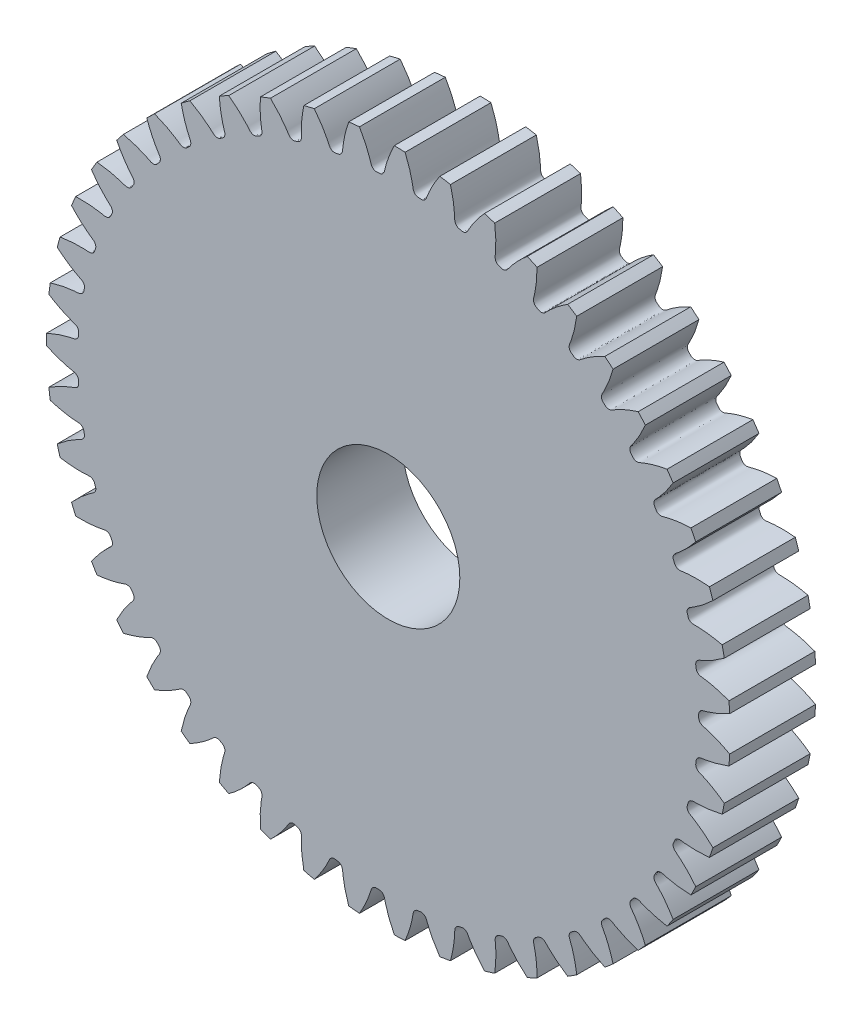
SolidWorks part; units mm, degrees
ref_plane "Front Plane" through (0, 0, 0) normal (0, 0, 1) x (1, 0, 0)
ref_plane "Top Plane" through (0, 0, 0) normal (0, 1, 0) x (1, 0, 0)
ref_plane "Right Plane" through (0, 0, 0) normal (1, 0, 0) x (0, 0, -1)
ref_axis "Axis1" through (0, 0, 55) along (0, 0, -1)
sketch "SketchRevolveSpurGear" plane through (0, 0, 0) normal (1, 0, 0) x (0, 0, -1)
  line L0 (0, 0) -> (1, 0) construction
  line L1 (-0.6, 0) -> (-0.6, 4.7775)
  line L2 (-0.6, 4.7775) -> (0.6, 4.7775)
  line L3 (0.6, 4.7775) -> (0.6, 0)
  line L4 (0.6, 0) -> (-0.6, 0)
  dimension "Side1" = 0.6
  dimension "OutsideRadius" = 4.7775
  dimension "Side2" = 0.6
revolve "SpurGear" add sketch "SketchRevolveSpurGear" angle 360 about L0
sketch "SketchToothSpurGear" plane through (0, 0, 0) normal (0, 0, 1) x (1, 0, 0)
  arc A0 (4.7808, 0.2492) -> (4.7808, -0.2492) centre (0, 0) cw
  spline S0 degree 3 poles (4.7808, -0.2492) (4.7634, -0.2397) (4.7377, -0.2259) (4.7034, -0.2086) (4.6788, -0.1966) (4.6549, -0.1854) (4.6316, -0.1749) (4.6091, -0.1651) (4.5872, -0.156) (4.5661, -0.1476) (4.5457, -0.1398) (4.526, -0.1326) (4.5071, -0.126) (4.489, -0.1199) (4.4717, -0.1144) (4.4552, -0.1095) (4.4272, -0.1013) (4.4005, -0.0961) (4.3781, -0.085) (4.3686, -0.079) (4.3587, -0.0706) (4.3487, -0.0584) (4.341, -0.0417) (4.3379, -0.0214) (4.3392, 0) (4.3379, 0.0214) (4.341, 0.0417) (4.3487, 0.0584) (4.3587, 0.0706) (4.3686, 0.079) (4.3781, 0.085) (4.4005, 0.0961) (4.4272, 0.1013) (4.4552, 0.1095) (4.4717, 0.1144) (4.489, 0.1199) (4.5071, 0.126) (4.526, 0.1326) (4.5457, 0.1398) (4.5661, 0.1476) (4.5872, 0.156) (4.6091, 0.1651) (4.6316, 0.1749) (4.6549, 0.1854) (4.6788, 0.1966) (4.7034, 0.2086) (4.7377, 0.2259) (4.7634, 0.2397) (4.7808, 0.2492) knots 0 0 0 0 0.055398 0.081807 0.107356 0.132045 0.155874 0.178843 0.200952 0.222201 0.242591 0.26212 0.280789 0.298599 0.315548 0.331638 0.346867 0.397347 0.406728 0.416895 0.428636 0.443004 0.46085 0.479253 0.5 0.520747 0.53915 0.556996 0.571364 0.583105 0.593272 0.602653 0.653133 0.668362 0.684452 0.701401 0.719211 0.73788 0.757409 0.777799 0.799048 0.821157 0.844126 0.867955 0.892644 0.918193 0.944602 1 1 1 1
extrude "ToothExtrudeCutSpurGear" cut sketch "SketchToothSpurGear" against normal blind 9.525 and the other way blind 9.525
pattern_circular "PatternSpurGear" count 47 every 7.66 about axis through (0, 0, 55) along (0, 0, -1) of "ToothExtrudeCutSpurGear"
sketch "BoreRevolveSketch" plane through (0, 0, 0) normal (1, 0, 0) x (0, 0, -1)
  line L0 (0, 0) -> (1, 0) construction
  line L1 (-9.525, 0) -> (9.525, 0)
  line L2 (9.525, 0) -> (9.525, 6.35)
  line L3 (9.525, 6.35) -> (-9.525, 6.35)
  line L4 (-9.525, 6.35) -> (-9.525, 0)
  dimension "BoreSide1" = 9.525
  dimension "TaperSide1" = 6.35
  dimension "BoreSide2" = 9.525
  dimension "TaperSide2" = 6.35
sketch "AuxiliarySketchSpurGear" plane through (0, 0, 0) normal (0, 0, 1) x (1, 0, 0)
  circle A0 centre (0, 0) radius 4.5825 construction
  circle A1 centre (0, 0) radius 4.3061 construction
  circle A2 centre (0, 0) radius 4.4134 construction
  circle A3 centre (0, 0) radius 4.7775 construction
  circle A4 centre (0, 0) radius 4.3387 construction
  dimension "PitchDiameter" = 9.165
  dimension "BaseDiameter" = 8.6123
  dimension "FormDiameter" = 8.8268
  dimension "MajorDiameter" = 9.555
  dimension "MinorDiameter" = 8.6775
sketch "Sketch6" plane through (0, 0, 0.6) normal (0, 0, 1) x (1, 0, 0)
  circle A0 centre (0, 0) radius 1
  dimension "D1" = 2
extrude "Cut-Extrude2" cut sketch "Sketch6" against normal blind 10
